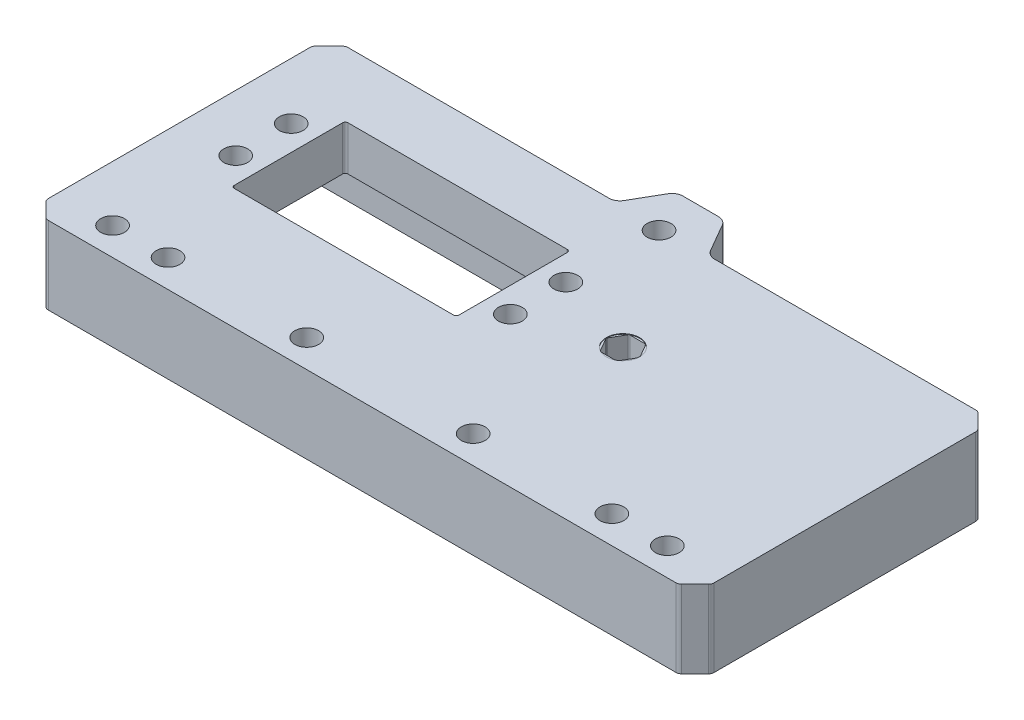
SolidWorks part; units mm, degrees
material "ABS"
ref_plane "前视基准面" through (0, 0, 0) normal (0, 0, 1) x (1, 0, 0)
ref_plane "上视基准面" through (0, 0, 0) normal (0, 1, 0) x (1, 0, 0)
ref_plane "右视基准面" through (0, 0, 0) normal (1, 0, 0) x (0, 0, -1)
other "Configuration Table"
sketch "草图1" plane through (0, 0, 0) normal (0, 1, 0) x (1, 0, 0)
  line L0 (0, 0) -> (10.05, 0) construction
  line L1 (-24.75, -5) -> (24.75, -5) construction
  line L2 (-24.75, -5) -> (-24.75, 5) construction
  line L3 (-24.75, 5) -> (24.75, 5) construction
  line L4 (24.75, -5) -> (24.75, 5) construction
  line L5 (-24.75, -5) -> (24.75, 5) construction
  line L6 (-24.75, 5) -> (24.75, -5) construction
  line L7 (19.75, -10.25) -> (-19.75, -10.25)
  line L8 (20.25, -9.75) -> (20.25, 9.75)
  line L9 (19.75, 10.25) -> (-19.75, 10.25)
  line L10 (-20.25, -9.75) -> (-20.25, 9.75)
  line L11 (20.25, -10.25) -> (-20.25, 10.25) construction
  line L12 (20.25, 10.25) -> (-20.25, -10.25) construction
  line L13 (10.05, 0) -> (40.05, 0) construction
  line L14 (25.05, 0) -> (25.05, 22) construction
  line L15 (42.9945, 0.15) -> (41.6521, 2.475)
  line L16 (41.3923, 2.625) -> (38.7077, 2.625)
  line L17 (38.4479, 2.475) -> (37.1055, 0.15)
  line L18 (37.1055, -0.15) -> (38.4479, -2.475)
  line L19 (38.7077, -2.625) -> (41.3923, -2.625)
  line L20 (41.6521, -2.475) -> (42.9945, -0.15)
  line L22 (85.05, -22) -> (-34.95, -22)
  line L23 (85.05, -22) -> (85.05, 22)
  line L24 (85.05, 22) -> (-34.95, 22)
  line L25 (-34.95, -22) -> (-34.95, 22)
  line L26 (85.05, -22) -> (-34.95, 22) construction
  line L27 (85.05, 22) -> (-34.95, -22) construction
  circle A0 centre (-24.75, 5) radius 2.15
  circle A1 centre (-24.75, -5) radius 2.15
  circle A2 centre (24.75, -5) radius 2.15
  circle A3 centre (24.75, 5) radius 2.15
  arc A4 (20.25, 9.75) -> (19.75, 10.25) centre (19.75, 9.75) ccw
  arc A5 (19.75, -10.25) -> (20.25, -9.75) centre (19.75, -9.75) ccw
  arc A6 (-19.75, -10.25) -> (-20.25, -9.75) centre (-19.75, -9.75) cw
  arc A7 (-19.75, 10.25) -> (-20.25, 9.75) centre (-19.75, 9.75) ccw
  circle A8 centre (40.05, 0) radius 2.625 construction
  arc A9 (37.1055, 0.15) -> (37.1055, -0.15) centre (37.3653, 0) ccw
  arc A10 (38.4479, -2.475) -> (38.7077, -2.625) centre (38.7077, -2.325) ccw
  arc A11 (41.3923, -2.625) -> (41.6521, -2.475) centre (41.3923, -2.325) ccw
  arc A12 (42.9945, 0.15) -> (42.9945, -0.15) centre (42.7347, 0) cw
  arc A13 (41.6521, 2.475) -> (41.3923, 2.625) centre (41.3923, 2.325) ccw
  arc A14 (38.7077, 2.625) -> (38.4479, 2.475) centre (38.7077, 2.325) ccw
  point P0 (0, 0)
  point P10 (0, 0)
  dimension "D1" = 4.3
  dimension "D6" = 0.5
  dimension "D9" = 5.25
  dimension "D10" = 0.3
  dimension "D2" = 10
  dimension "D3" = 49.5
  dimension "D4" = 40.5
  dimension "D5" = 20.5
  dimension "D7" = 10.05
  dimension "D8" = 30
  dimension "D11" = 22
  dimension "D12" = 44
  dimension "D13" = 120
extrude "凸台-拉伸1" add sketch "草图1" along normal blind 8
sketch "草图2" plane through (0, 8, 0) normal (0, 1, 0) x (1, 0, 0)
  line L0 (40.05, 0) -> (40.05, 2.625) construction
  line L1 (41.3923, 2.625) -> (38.7077, 2.625) construction
  line L3 (40.05, 0) -> (37.7767, -1.3125) construction
  line L4 (37.1055, -0.15) -> (38.4479, -2.475) construction
  circle A0 centre (40.05, 0) radius 3
  dimension "D1" = 6
extrude "切除-拉伸1" cut sketch "草图2" against normal blind 0.1
other "移动面1" face at (25.05, 4, 22) offset 10 parameters "D1"=10
sketch "草图3" plane through (0, 0, 0) normal (0, -1, 0) x (1, 0, 0)
  line L0 (38.7077, 2.625) -> (41.3923, 2.625) construction
  line L1 (29, -11) -> (-29, -11)
  line L2 (29, -11) -> (29, 11)
  line L3 (29, 11) -> (-29, 11)
  line L4 (-29, -11) -> (-29, 11)
  line L5 (29, -11) -> (-29, 11) construction
  line L6 (29, 11) -> (-29, -11) construction
  line L7 (37.1055, 0.15) -> (38.4479, 2.475) construction
  line L8 (38.4479, -2.475) -> (37.1055, -0.15) construction
  line L9 (41.3923, -2.625) -> (38.7077, -2.625) construction
  line L10 (-34.95, 32) -> (-34.95, -22)
  line L11 (-34.95, -22) -> (85.05, -22)
  line L12 (85.05, -22) -> (85.05, 32)
  line L13 (85.05, 32) -> (-34.95, 32)
  line L14 (-34.95, 32) -> (-34.95, -22)
  line L15 (-34.95, -22) -> (85.05, -22)
  line L16 (85.05, -22) -> (85.05, 32)
  line L17 (85.05, 32) -> (-34.95, 32)
  line L18 (42.9945, -0.15) -> (41.6521, -2.475) construction
  line L19 (41.6521, 2.475) -> (42.9945, 0.15) construction
  line L20 (41.6521, 2.475) -> (42.9945, 0.15)
  line L21 (42.9945, -0.15) -> (41.6521, -2.475)
  line L22 (41.3923, -2.625) -> (38.7077, -2.625)
  line L23 (38.4479, -2.475) -> (37.1055, -0.15)
  line L24 (37.1055, 0.15) -> (38.4479, 2.475)
  line L25 (38.7077, 2.625) -> (41.3923, 2.625)
  arc A0 (38.7077, 2.625) -> (38.4479, 2.475) centre (38.7077, 2.325) ccw construction
  arc A1 (37.1055, 0.15) -> (37.1055, -0.15) centre (37.3653, 0) ccw construction
  arc A2 (38.4479, -2.475) -> (38.7077, -2.625) centre (38.7077, -2.325) ccw construction
  arc A3 (41.3923, -2.625) -> (41.6521, -2.475) centre (41.3923, -2.325) ccw construction
  arc A4 (42.9945, -0.15) -> (42.9945, 0.15) centre (42.7347, 0) ccw construction
  arc A5 (41.6521, 2.475) -> (41.3923, 2.625) centre (41.3923, 2.325) ccw construction
  arc A6 (41.6521, 2.475) -> (41.3923, 2.625) centre (41.3923, 2.325) ccw
  arc A7 (42.9945, -0.15) -> (42.9945, 0.15) centre (42.7347, 0) ccw
  arc A8 (41.3923, -2.625) -> (41.6521, -2.475) centre (41.3923, -2.325) ccw
  arc A9 (38.4479, -2.475) -> (38.7077, -2.625) centre (38.7077, -2.325) ccw
  arc A10 (37.1055, 0.15) -> (37.1055, -0.15) centre (37.3653, 0) ccw
  arc A11 (38.7077, 2.625) -> (38.4479, 2.475) centre (38.7077, 2.325) ccw
  point P0 (0, 0)
  dimension "D1" = 58
  dimension "D2" = 22
  dimension "D3" = 0
extrude "凸台-拉伸2" add sketch "草图3" along normal blind 6
sketch "草图4" plane through (0, -6, 0) normal (0, -1, 0) x (1, 0, 0)
  line L0 (25.05, 32) -> (25.05, -22) construction
  line L1 (85.05, 32) -> (-34.95, 32) construction
  line L2 (-34.95, -22) -> (85.05, -22) construction
  circle A0 centre (-24.95, 27) radius 2.15
  circle A1 centre (-14.95, 27) radius 2.15
  circle A2 centre (65.05, 27) radius 2.15
  circle A3 centre (75.05, 27) radius 2.15
  dimension "D1" = 5
  dimension "D2" = 4.3
  dimension "D3" = 50
  dimension "D4" = 2
extrude "切除-拉伸2" cut sketch "草图4" against normal through all
sketch "草图5" plane through (0, -6, 0) normal (0, -1, 0) x (1, 0, 0)
  line L0 (-8.95, 21) -> (59.05, 21)
  line L4 (29, 11) -> (-29, 11) construction
  line L5 (-33, -16) -> (33, -16)
  line L6 (-33, -16) -> (-33, 16)
  line L7 (-33, 16) -> (33, 16)
  line L8 (77.05, 24) -> (-26.95, 24)
  line L9 (-26.95, 24) -> (-26.95, -14)
  line L10 (-26.95, -14) -> (77.05, -14)
  line L11 (77.05, -14) -> (77.05, 24)
  line L12 (77.05, 24) -> (-26.95, 24)
  line L13 (-26.95, 24) -> (-26.95, -14)
  line L14 (-26.95, -14) -> (77.05, -14)
  line L15 (77.05, -14) -> (77.05, 24)
  line L16 (33, -16) -> (33, 16)
  line L17 (-33, -16) -> (33, 16) construction
  line L18 (-33, 16) -> (33, -16) construction
  line L19 (29, -11) -> (29, 11) construction
  line L20 (40.05, 0) -> (0, 0) construction
  line L21 (40.05, 0) -> (40.05, 2.625) construction
  line L22 (41.3923, 2.625) -> (38.7077, 2.625) construction
  line L23 (25.05, 32) -> (25.05, -22) construction
  line L24 (-34.95, 32) -> (-8.95, 32)
  line L25 (-34.95, 32) -> (-34.95, 21)
  line L26 (-34.95, 21) -> (-8.95, 21)
  line L27 (-8.95, 32) -> (-8.95, 21)
  line L28 (85.05, 32) -> (-34.95, 32) construction
  line L29 (-34.95, -22) -> (85.05, -22) construction
  line L30 (85.05, 21) -> (59.05, 21)
  line L31 (59.05, 32) -> (59.05, 21)
  line L32 (85.05, 32) -> (59.05, 32)
  line L33 (85.05, 32) -> (85.05, 21)
  circle A0 centre (40.05, 0) radius 9
  circle A1 centre (-14.95, 27) radius 2.15 construction
  point P0 (0, 0)
  dimension "D4" = 18
  dimension "D2" = 5
  dimension "D3" = 4
  dimension "D5" = 6
  dimension "D6" = 6
  dimension "D1" = 8
extrude "切除-拉伸3" cut sketch "草图5" against normal blind 8 contours A0 L16 L14 L15 L30 L31 L12 L27 L26 L13 L7 region at (47.4615, -6, 6.8302)
fillet "圆角1" radius 2 7 edges at (33, -2, 16) (77.05, -2, 21) (77.05, -2, -14) (-26.95, -2, 21) (33, -2, -14) (-26.95, -2, 16) (33, -2, 5.5944)
fillet "圆角2" radius 2 1 edges at (33, -2, -5.5944)
fillet "圆角4" radius 1 4 edges at (29, -3, -11) (29, -3, 11) (-29, -3, -11) (-29, -3, 11)
chamfer "倒角1" distance 3 angle 45 4 edges at (85.05, 1, 32) (85.05, 1, -22) (-34.95, 1, 32) (-34.95, 1, -22)
fillet "圆角5" radius 1 8 edges at (-31.95, 1, 32) (-34.95, 1, 29) (-34.95, 1, -19) (-31.95, 1, -22) (85.05, 1, -19) (85.05, 1, 29) (82.05, 1, 32) (82.05, 1, -22)
sketch "草图6" plane through (0, -6, 0) normal (0, -1, 0) x (1, 0, 0)
  line L0 (25.05, -22) -> (25.05, -21.5) construction
  line L1 (-31.5358, -22) -> (81.6358, -22) construction
  line L3 (33.7103, -21.5) -> (29.3801, -14)
  line L4 (29.3801, -14) -> (20.7199, -14)
  line L5 (20.7199, -14) -> (16.3897, -21.5)
  line L6 (16.3897, -21.5) -> (20.7199, -29)
  line L7 (20.7199, -29) -> (29.3801, -29)
  line L8 (29.3801, -29) -> (33.7103, -21.5)
  circle A0 centre (25.05, -21.5) radius 7.5 construction
  circle A1 centre (25.05, -21.5) radius 2.15
  dimension "D1" = 15
  dimension "D3" = 4.3
  dimension "D2" = 0.5
extrude "凸台-拉伸3" add sketch "草图6" against normal up to surface (14 mm away) up to face at (-24.95, 8, 24.85)
extrude "切除-拉伸6" cut sketch "草图6<3>" against normal through all contours A1 region at (25.05, -6, -21.5)
sketch "草图6<3>" plane through (0, -6, 0) normal (0, -1, 0) x (1, 0, 0) same geometry as "草图6"
fillet "圆角6" radius 2 4 edges at (20.7199, 1, -29) (29.3801, 1, -29) (33.4216, 1, -22) (16.6784, 1, -22)
chamfer "倒角2" distance 1 angle 45 40 edges at (32.4142, 2, 15.4142) (3.025, 2, 16) (-26.95, 2, 18.5) (-26.3642, 2, 20.4142) (25.05, 2, 21) (76.4642, 2, 20.4142) (77.05, 2, 3.5) (76.4642, 2, -13.4142) (55.025, 2, -14) (33.5858, 2, -13.4142) (33, 2, -10.8861) (33.9599, 2, -8.064) (49.05, 2, 0) (33, 2, 11.8861) (0, -6, -11) (28.7071, -6, -10.7071) (-28.7071, -6, -10.7071) (29, -6, 0) (-29, -6, 0) (28.7071, -6, 10.7071) (-28.7071, -6, 10.7071) (0, -6, 11) (49.05, -6, 0) (33.9599, -6, -8.064) (33, -6, -10.8861) (33, -6, 11.8861) (33.5858, -6, -13.4142) (32.4142, -6, 15.4142) (55.025, -6, -14) (3.025, -6, 16) (76.4642, -6, -13.4142) (77.05, -6, 3.5) (-26.95, -6, 18.5) (76.4642, -6, 20.4142) (-26.3642, -6, 20.4142) (25.05, -6, 21) (33.9599, 2, 8.064) (-26.3642, 2, 16.5858) (33.9599, -6, 8.064) (-26.3642, -6, 16.5858)
sketch "Sketch1" plane through (0, -6, 0) normal (0, -1, 0) x (1, 0, 0)
  circle A0 centre (40.0742, 0) radius 5.2813
extrude "Boss-Extrude1" add sketch "Sketch1" against normal blind 4
sketch "草图7" plane through (0, -6, 0) normal (0, -1, 0) x (1, 0, 0)
  line L0 (25.05, 32) -> (25.05, -21.5) construction
  line L1 (81.6358, 32) -> (-31.5358, 32) construction
  line L2 (-14.95, 27) -> (25.05, 27) construction
  circle A0 centre (10.05, 27) radius 2.15
  circle A1 centre (40.05, 27) radius 2.15
  dimension "D1" = 4.3
  dimension "D2" = 15
extrude "切除-拉伸7" cut sketch "草图7" against normal through all
